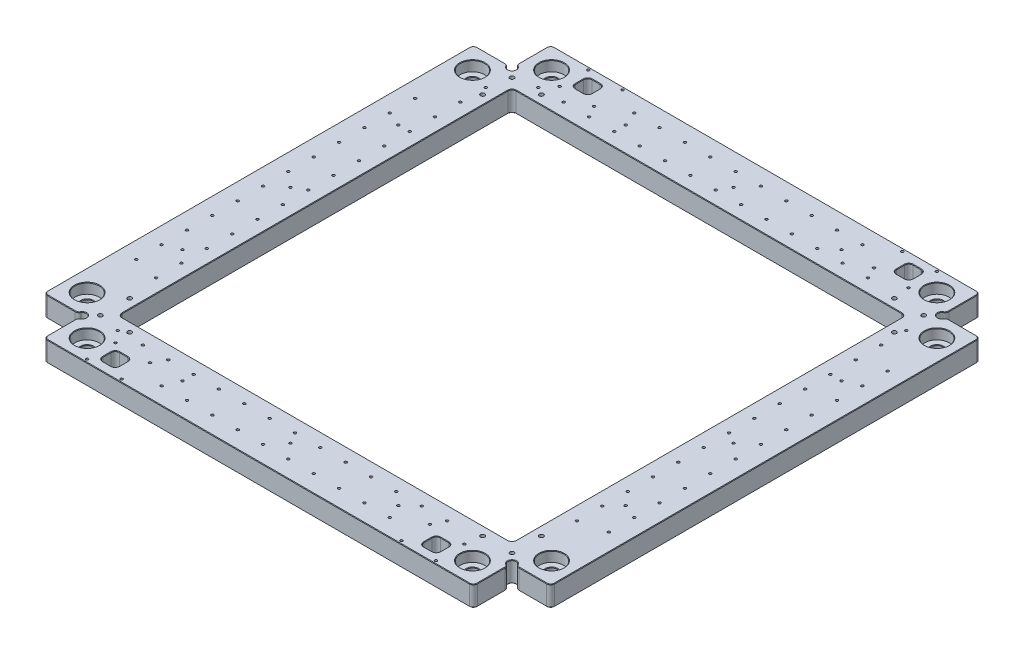
SolidWorks part; units mm, degrees
note: '?' marks a value the reader was unsure of.
material "ASTM A36 Steel"
ref_plane "Front Plane" through (0, 0, 0) normal (0, 0, 1) x (1, 0, 0)
ref_plane "Top Plane" through (0, 0, 0) normal (0, 1, 0) x (1, 0, 0)
ref_plane "Right Plane" through (0, 0, 0) normal (1, 0, 0) x (0, 0, -1)
sketch "Sketch1" plane through (0, 0, 0) normal (0, 1, 0) x (1, 0, 0)
  line L1 (250, -250) -> (-250, -250)
  line L2 (250, -250) -> (250, 250)
  line L3 (250, 250) -> (-250, 250)
  line L4 (-250, -250) -> (-250, 250)
  line L5 (250, -250) -> (-250, 250) construction
  line L6 (250, 250) -> (-250, -250) construction
  point P0 (0, 0)
  dimension "D1" = 500
  dimension "D2" = 500
extrude "Boss-Extrude1" add sketch "Sketch1" along normal blind 20
sketch "Sketch2" plane through (0, 20, 0) normal (0, 1, 0) x (1, 0, 0)
  line L0 (250, 250) -> (-250, 250) construction
  line L10 (-250, 250) -> (-250, -250) construction
  line L15 (-250, 169) -> (-208, 169)
  line L16 (-250, 169) -> (-250, 211)
  line L17 (-174.5, 213.5) -> (-205.5, 213.5)
  line L27 (-250, 211) -> (-208, 211)
  line L33 (-208, 169) -> (-208, 211)
  line L35 (-250, 169) -> (-208, 211) construction
  line L36 (-250, 211) -> (-208, 169) construction
  line L37 (-169, 208) -> (-211, 208)
  line L38 (-169, 208) -> (-169, 250)
  line L39 (-169, 250) -> (-211, 250)
  line L40 (-211, 208) -> (-211, 250)
  line L41 (-169, 208) -> (-211, 250) construction
  line L42 (-169, 250) -> (-211, 208) construction
  line L43 (-208, 206) -> (-213, 211)
  line L44 (-174.5, 213.5) -> (-174.5, 244.5)
  line L45 (-174.5, 244.5) -> (-205.5, 244.5)
  line L46 (-205.5, 213.5) -> (-205.5, 244.5)
  line L47 (-174.5, 213.5) -> (-205.5, 244.5) construction
  line L48 (-174.5, 244.5) -> (-205.5, 213.5) construction
  line L49 (-213.5, 174.5) -> (-244.5, 174.5)
  line L50 (-213.5, 174.5) -> (-213.5, 205.5)
  line L51 (-213.5, 205.5) -> (-244.5, 205.5)
  line L52 (-244.5, 174.5) -> (-244.5, 205.5)
  line L53 (-213.5, 174.5) -> (-244.5, 205.5) construction
  line L54 (-213.5, 205.5) -> (-244.5, 174.5) construction
  line L55 (-206, 208) -> (-211, 213)
  line L56 (-213, 211) -> (-211, 213) construction
  point P1 (-229, 190)
  point P5 (-190, 229)
  point P23 (-229, 190)
  point P27 (-190, 229)
  dimension "D1" = 5
  dimension "D2" = 45
  dimension "D3" = 42
  dimension "D4" = 31
  dimension "D5" = 45
  dimension "D6" = 5
  dimension "D7" = 60
hole_wizard "Bearing Press Fit" positions "Sketch8" profile "Sketch9" hole size "Ø11.8" standard "ANSI Metric" end condition through all
sketch "Sketch8" plane through (0, 20, 0) normal (0, 1, 0) x (1, 0, 0)
  line L1 (-169, 250) -> (-211, 208) construction
  point P8 (-190, 229)
  point P12 (-229, 190)
sketch "Sketch9" plane through (-190, 20, -229) normal (1, 0, 0) x (0, 0, 1)
  line L0 (0, 0) -> (0, 20)
  line L1 (0, 20) -> (5.9, 20)
  line L2 (5.9, 20) -> (5.9, 0)
  line L5 (5.9, 0) -> (0, 0)
  line L11 (0, -6.35) -> (0, 107.95) construction
  dimension "Thru Hole Dia." = 11.8
  dimension "Thru Hole Depth" = 20
ref_axis "Axis1" through (0, 21, 0) along (0, -1, 0)?
pattern_circular "CirPattern1" count 4 over 360 about axis through (0, 0, 0) along (0, 1, 0) of "Bearing Press Fit"
sketch "Sketch5" plane through (0, 20, 0) normal (0, 1, 0) x (1, 0, 0)
  line L1 (194, -194) -> (-194, -194)
  line L2 (194, -194) -> (194, 194)
  line L3 (194, 194) -> (-194, 194)
  line L4 (-194, -194) -> (-194, 194)
  line L5 (194, -194) -> (-194, 194) construction
  line L6 (194, 194) -> (-194, -194) construction
  point P0 (0, 0)
  dimension "D1" = 388
extrude "Cut-Extrude1" cut sketch "Sketch5" against normal up to surface (20 mm away) up to face at (-229, 0, 195.9)
sketch "Sketch10" plane through (0, 0, 0) normal (0, 1, 0) x (1, 0, 0)
  line L5 (194, 194) -> (-194, 194) construction
  line L6 (214, -214) -> (-214, -214)
  line L14 (214, -214) -> (214, 214)
  line L15 (214, 214) -> (-214, 214)
  line L16 (-214, -214) -> (-214, 214)
  line L17 (214, -214) -> (-214, 214) construction
  line L18 (214, 214) -> (-214, -214) construction
  line L19 (201.5, -201.5) -> (-201.5, -201.5)
  line L20 (201.5, -201.5) -> (201.5, 201.5)
  line L21 (201.5, 201.5) -> (-201.5, 201.5)
  line L22 (-201.5, -201.5) -> (-201.5, 201.5)
  line L23 (201.5, -201.5) -> (-201.5, 201.5) construction
  line L24 (201.5, 201.5) -> (-201.5, -201.5) construction
  point P0 (0, 0)
  point P6 (0, 0)
  dimension "D2" = 7.5
  dimension "D1" = 12.5
extrude "Linear Rail Slot" cut sketch "Sketch10" along normal blind 2.5
fillet "Fillet2" radius 4 4 edges at (-194, 10, 194) (194, 10, 194) (194, 10, -194) (-194, 10, -194)
sketch "Sketch11" plane through (0, 2.5, 0) normal (0, -1, 0) x (1, 0, 0)
  line L0 (-204, 207.5) -> (156, 207.5)
  line L1 (-201.5, 201.5) -> (201.5, 201.5) construction
  line L3 (-214, -214) -> (-214, 214) construction
  point P16 (143.5, 207.5)
  point P18 (118.5, 207.5)
  point P19 (93.5, 207.5)
  point P20 (68.5, 207.5)
  point P21 (43.5, 207.5)
  point P22 (18.5, 207.5)
  point P23 (-6.5, 207.5)
  point P24 (-31.5, 207.5)
  point P25 (-56.5, 207.5)
  point P26 (-81.5, 207.5)
  point P28 (-106.5, 207.5)
  point P29 (-131.5, 207.5)
  point P30 (-156.5, 207.5)
  point P31 (-181.5, 207.5)
  dimension "D1" = 360
  dimension "D2" = 6
  dimension "D4" = 14
  dimension "D5" = 25
  dimension "D6" = 10
  dimension "D3" = 12.5
hole_wizard "Tap Drill for M3x0.5 Tap1" positions "Sketch12" profile "Sketch13" hole size "M3x0.5" standard "ANSI Metric" end condition through all
sketch "Sketch12" plane through (0, 2.5, 0) normal (0, -1, 0) x (-1, 0, 0)
  line L0 (204, -207.5) -> (-156, -207.5) construction
  point P28 (-143.5, -207.5)
  point P31 (-118.5, -207.5)
  point P34 (-93.5, -207.5)
  point P37 (-68.5, -207.5)
  point P40 (-43.5, -207.5)
  point P43 (-18.5, -207.5)
  point P46 (6.5, -207.5)
  point P49 (31.5, -207.5)
  point P51 (56.5, -207.5)
  point P54 (81.5, -207.5)
  point P57 (106.5, -207.5)
  point P61 (131.5, -207.5)
  point P64 (156.5, -207.5)
  point P67 (181.5, -207.5)
sketch "Sketch13" plane through (143.5, 2.5, 207.5) normal (1, 0, 0) x (0, 0, -1)
  line L0 (0, 0) -> (0, 17.5)
  line L1 (0, 17.5) -> (1.25, 17.5)
  line L2 (1.25, 17.5) -> (1.25, 0)
  line L5 (1.25, 0) -> (0, 0)
  line L11 (0, -6.35) -> (0, 107.95) construction
  dimension "Thru Hole Dia." = 2.5
  dimension "Thru Hole Depth" = 17.5
sketch "Sketch14" plane through (0, 0, 0) normal (0, -1, 0) x (1, 0, 0)
  line L1 (-156.5, 213.5) -> (-181.5, 213.5)
  line L2 (-152.5, 217.5) -> (-152.5, 219.5)
  line L3 (-156.5, 223.5) -> (-181.5, 223.5)
  line L4 (-185.5, 217.5) -> (-185.5, 219.5)
  line L5 (-152.5, 213.5) -> (-185.5, 223.5) construction
  line L6 (-152.5, 223.5) -> (-185.5, 213.5) construction
  line L7 (-201.5, 201.5) -> (201.5, 201.5) construction
  line L8 (-181.5, 207.5) -> (-156.5, 207.5) construction
  line L19 (-6.5, 213.5) -> (-31.5, 213.5)
  line L25 (-2.5, 217.5) -> (-2.5, 219.5)
  line L26 (-6.5, 223.5) -> (-31.5, 223.5)
  line L31 (-35.5, 217.5) -> (-35.5, 219.5)
  line L32 (-2.5, 213.5) -> (-35.5, 223.5) construction
  line L33 (-2.5, 223.5) -> (-35.5, 213.5) construction
  line L34 (-31.5, 207.5) -> (-6.5, 207.5) construction
  line L35 (143.5, 213.5) -> (118.5, 213.5)
  line L36 (147.5, 217.5) -> (147.5, 219.5)
  line L37 (143.5, 223.5) -> (118.5, 223.5)
  line L38 (114.5, 217.5) -> (114.5, 219.5)
  line L39 (147.5, 213.5) -> (114.5, 223.5) construction
  line L40 (147.5, 223.5) -> (114.5, 213.5) construction
  line L41 (118.5, 207.5) -> (143.5, 207.5) construction
  arc A3 (-152.5, 219.5) -> (-156.5, 223.5) centre (-156.5, 219.5) ccw
  arc A4 (-156.5, 213.5) -> (-152.5, 217.5) centre (-156.5, 217.5) ccw
  arc A5 (-181.5, 213.5) -> (-185.5, 217.5) centre (-181.5, 217.5) cw
  arc A6 (-181.5, 223.5) -> (-185.5, 219.5) centre (-181.5, 219.5) ccw
  arc A7 (-2.5, 219.5) -> (-6.5, 223.5) centre (-6.5, 219.5) ccw
  arc A8 (-6.5, 213.5) -> (-2.5, 217.5) centre (-6.5, 217.5) ccw
  arc A9 (-31.5, 213.5) -> (-35.5, 217.5) centre (-31.5, 217.5) cw
  arc A10 (-31.5, 223.5) -> (-35.5, 219.5) centre (-31.5, 219.5) ccw
  arc A11 (147.5, 219.5) -> (143.5, 223.5) centre (143.5, 219.5) ccw
  arc A12 (143.5, 213.5) -> (147.5, 217.5) centre (143.5, 217.5) ccw
  arc A13 (118.5, 213.5) -> (114.5, 217.5) centre (118.5, 217.5) cw
  arc A14 (118.5, 223.5) -> (114.5, 219.5) centre (118.5, 219.5) ccw
  point P0 (-169, 218.5)
  point P12 (-169, 207.5)
  point P26 (-19, 218.5)
  point P45 (131, 218.5)
  dimension "D5" = 3
  dimension "D4" = 4
  dimension "D1" = 33
  dimension "D2" = 12
  dimension "D3" = 10
  dimension "D7" = 25
  dimension "D6" = 150
mirror "Mirror5" about plane through (0, 0, 0) normal (0, 0, 1) of "Tap Drill for M3x0.5 Tap1"
ref_plane "Plane1" through (0, 0, 0) normal (-0.7071, 0, 0.7071) x (0.7071, 0, 0.7071)
mirror "Mirror6" about plane through (0, 0, 0) normal (-0.7071, 0, 0.7071) of "Mirror5", "Tap Drill for M3x0.5 Tap1"
sketch "Sketch19" plane through (0, 2.5, 0) normal (0, -1, 0) x (1, 0, 0)
  line L0 (-198.5, 201.5) -> (-198.5, 214)
  line L1 (-201.5, 201.5) -> (201.5, 201.5) construction
  line L2 (-214, 214) -> (214, 214) construction
  line L3 (-198.5, 214) -> (-214, 214)
  line L4 (-214, 214) -> (-214, 198.5)
  line L5 (-214, -214) -> (-214, 214) construction
  line L6 (-214, 198.5) -> (-201.5, 198.5)
  line L7 (-201.5, -201.5) -> (-201.5, 201.5) construction
  line L8 (-201.5, 198.5) -> (-201.5, 201.5)
  line L9 (-201.5, 201.5) -> (-198.5, 201.5)
  dimension "D1" = 3
extrude "Boss-Extrude2" add sketch "Sketch19" along normal up to surface (2.5 mm away) up to face at (-229, 0, 195.9)
pattern_circular "CirPattern4" count 4 over 360 about axis through (0, 0, 0) along (0, 1, 0) of "Boss-Extrude2"
sketch "Sketch20" plane through (0, 20, 0) normal (0, 1, 0) x (1, 0, 0)
  line L5 (-250, -250) -> (250, -250) construction
  line L20 (150.3, -225) -> (166.3, -241) construction
  line L23 (166.3, -225) -> (150.3, -241) construction
  line L28 (122, -247) -> (172, -219) construction
  line L29 (172, -247) -> (122, -219) construction
  line L30 (172, -219) -> (122, -219) construction
  line L31 (122, -247) -> (122, -219) construction
  line L32 (172, -247) -> (122, -247) construction
  line L33 (172, -247) -> (172, -219) construction
  line L34 (162.3, -241) -> (154.3, -241)
  line L35 (150.3, -229) -> (150.3, -237)
  line L36 (162.3, -225) -> (154.3, -225)
  line L37 (166.3, -229) -> (166.3, -237)
  arc A12 (154.3, -225) -> (150.3, -229) centre (154.3, -229) ccw
  arc A13 (150.3, -237) -> (154.3, -241) centre (154.3, -237) ccw
  arc A14 (166.3, -237) -> (162.3, -241) centre (162.3, -237) cw
  arc A15 (166.3, -229) -> (162.3, -225) centre (162.3, -229) ccw
  circle A16 centre (190, -229) radius 5.9 construction
  point P65 (158.3, -233)
  point P66 (147, -233)
  point P67 (158.3, -233)
  dimension "D7" = 31.7
  dimension "D8" = 11.3
  dimension "D6" = 4
  dimension "D1" = 28
  dimension "D2" = 50
  dimension "D3" = 17
  dimension "D4" = 16
  dimension "D5" = 16
extrude "Cut-Extrude3" cut sketch "Sketch20" against normal through all
hole_wizard "Tap Drill for M3x0.5 Tap6" positions "Sketch39" profile "Sketch40" hole size "M3x0.5" standard "ANSI Metric" end condition through all
sketch "Sketch39" plane through (0, 20, 0) normal (0, 1, 0) x (1, 0, 0)
  line L1 (172, -247) -> (138, -247)
  line L2 (172, -247) -> (172, -219)
  line L3 (172, -219) -> (138, -219)
  line L4 (138, -247) -> (138, -219)
  line L5 (-250, -250) -> (250, -250) construction
  circle A0 centre (190, -229) radius 5.9 construction
  point P1 (172, -247)
  point P2 (138, -219)
  point P99 (172, -219)
  point P100 (138, -247)
  dimension "D1" = 34
  dimension "D2" = 28
  dimension "D3" = 3
  dimension "D4" = 18
sketch "Sketch40" plane through (172, 20, 247) normal (1, 0, 0) x (0, 0, 1)
  line L0 (0, 0) -> (0, 20)
  line L1 (0, 20) -> (1.25, 20)
  line L2 (1.25, 20) -> (1.25, 0)
  line L5 (1.25, 0) -> (0, 0)
  line L11 (0, -6.35) -> (0, 107.95) construction
  dimension "Thru Hole Dia." = 2.5
  dimension "Thru Hole Depth" = 20
mirror "Mirror8" about plane through (0, 0, 0) normal (1, 0, 0) of "Tap Drill for M3x0.5 Tap6", "Cut-Extrude3"
mirror "Mirror9" about plane through (0, 0, 0) normal (0, 0, 1) of "Mirror8", "Cut-Extrude3", "Tap Drill for M3x0.5 Tap6"
sketch "Sketch27" plane through (0, 20, 0) normal (0, 1, 0) x (1, 0, 0)
  line L1 (250, -250) -> (211.9, -250)
  line L2 (250, -250) -> (250, -211.9)
  line L3 (250, -211.9) -> (211.9, -211.9)
  line L4 (211.9, -250) -> (211.9, -211.9)
  dimension "D1" = 38.1
extrude "Cut-Extrude4" cut sketch "Sketch27" against normal up to surface (20 mm away) up to face at (172, 0, -245.75)
sketch "Sketch47" plane through (0, 0, 0) normal (0, -1, 0) x (1, 0, 0)
  circle A0 centre (211.9, 211.9) radius 4
  dimension "D1" = 8
extrude "Cut-Extrude5" cut sketch "Sketch47" against normal up to surface (20 mm away) up to face at (70.6333, 20, 70.6333)
hole_wizard "Tap Drill for M5x0.8 Tap1" positions "Sketch50" profile "Sketch49" hole size "M5x0.8" standard "ANSI Metric"
sketch "Sketch50" plane through (0, 20, 0) normal (0, 1, 0) x (1, 0, 0)
  line L0 (250, -211.9) -> (250, 250) construction
  line L1 (-250, -250) -> (211.9, -250) construction
  line L2 (174, -203) -> (203, -203) construction
  line L3 (203, -203) -> (203, -174) construction
  point P0 (174, -203)
  point P2 (203, -203)
  point P4 (203, -174)
  dimension "D1" = 47
  dimension "D2" = 29
  dimension "D3" = 47
sketch "Sketch49" plane through (174, 20, 203) normal (1, 0, 0) x (0, 0, 1)
  line L0 (0, 0) -> (0, 11.2618)
  line L1 (0, 11.2618) -> (2.1, 10)
  line L2 (2.1, 10) -> (2.1, 0)
  line L5 (2.1, 0) -> (0, 0)
  line L10 (0, 11.2618) -> (-2.1, 10) construction
  line L11 (0, -6.35) -> (0, 107.95) construction
  dimension "Hole Dia." = 4.2
  dimension "Hole Depth" = 10
  dimension "Drill Angle" = 118
sketch "Sketch53" plane through (0, 0, 0) normal (0, -1, 0) x (1, 0, 0)
  line L0 (-150.3, 233) -> (150.3, 233) construction
  line L1 (-150.3, 229) -> (-150.3, 237) construction
  line L2 (150.3, 229) -> (150.3, 237) construction
  line L3 (-112.5, 233) -> (-166.3, 233) construction
  line L4 (-166.3, 237) -> (-166.3, 229) construction
  line L5 (112.5, 233) -> (166.3, 233) construction
  line L6 (166.3, 237) -> (166.3, 229) construction
  point P6 (-112.5, 233)
  point P7 (-87.5, 233)
  point P9 (-62.5, 233)
  point P10 (-37.5, 233)
  point P11 (-12.5, 233)
  point P12 (12.5, 233)
  point P13 (37.5, 233)
  point P14 (62.5, 233)
  point P15 (87.5, 233)
  point P16 (112.5, 233)
  point P26 (137.5, 233)
  dimension "D3" = 25
  dimension "D2" = 11
hole_wizard "Tap Drill for M3x0.5 Tap7" positions "Sketch54" profile "Sketch56" hole size "M3x0.5" standard "ANSI Metric" end condition through all
sketch "Sketch54" plane through (0, 0, 0) normal (0, -1, 0) x (-1, 0, 0)
  point P0 (-112.5, -233)
  point P3 (-87.5, -233)
  point P6 (-62.5, -233)
  point P9 (-37.5, -233)
  point P12 (-12.5, -233)
  point P15 (12.5, -233)
  point P18 (37.5, -233)
  point P21 (62.5, -233)
  point P24 (87.5, -233)
  point P27 (112.5, -233)
sketch "Sketch56" plane through (112.5, 0, 233) normal (1, 0, 0) x (0, 0, -1)
  line L0 (0, 0) -> (0, 20)
  line L1 (0, 20) -> (1.25, 20)
  line L2 (1.25, 20) -> (1.25, 0)
  line L5 (1.25, 0) -> (0, 0)
  line L11 (0, -6.35) -> (0, 107.95) construction
  dimension "Thru Hole Dia." = 2.5
  dimension "Thru Hole Depth" = 20
sketch "Sketch59" plane through (0, 0, 0) normal (0, -1, 0) x (1, 0, 0)
  line L0 (-198.5, 201.5) -> (198.5, 201.5) construction
  line L4 (-94, 213.5) -> (-119, 213.5)
  line L5 (-90, 217.5) -> (-90, 219.5)
  line L6 (-94, 223.5) -> (-119, 223.5)
  line L7 (-123, 217.5) -> (-123, 219.5)
  line L8 (-90, 213.5) -> (-123, 223.5) construction
  line L9 (-90, 223.5) -> (-123, 213.5) construction
  line L10 (-106.5, 207.5) -> (-106.5, 218.5) construction
  line L11 (-12.5, 233) -> (12.5, 233) construction
  arc A2 (-90, 219.5) -> (-94, 223.5) centre (-94, 219.5) ccw
  arc A3 (-94, 213.5) -> (-90, 217.5) centre (-94, 217.5) ccw
  arc A4 (-119, 213.5) -> (-123, 217.5) centre (-119, 217.5) cw
  arc A5 (-119, 223.5) -> (-123, 219.5) centre (-119, 219.5) ccw
  point P0 (-106.5, 218.5)
  dimension "D1" = 10
  dimension "D4" = 4
  dimension "D2" = 33
  dimension "D3" = 12
extrude "Cut-Extrude6" cut sketch "Sketch59" against normal blind 3.5
hole_wizard "Tap Drill for M3x0.5 Tap9" positions "Sketch62" profile "Sketch63" hole size "M3x0.5" standard "ANSI Metric" end condition through all
sketch "Sketch62" plane through (0, 3.5, 0) normal (0, -1, 0) x (-1, 0, 0)
  line L0 (90, -218.5) -> (123, -218.5) construction
  line L1 (90, -217.5) -> (90, -219.5) construction
  line L2 (123, -219.5) -> (123, -217.5) construction
  point P9 (106.5, -218.5)
sketch "Sketch63" plane through (-106.5, 3.5, 218.5) normal (1, 0, 0) x (0, 0, -1)
  line L0 (0, 0) -> (0, 16.5)
  line L1 (0, 16.5) -> (1.25, 16.5)
  line L2 (1.25, 16.5) -> (1.25, 0)
  line L5 (1.25, 0) -> (0, 0)
  line L11 (0, -6.35) -> (0, 107.95) construction
  dimension "Thru Hole Dia." = 2.5
  dimension "Thru Hole Depth" = 16.5
pattern_linear "LPattern1" count 3 spacing 106.5 along (1, 0, 0) of "Cut-Extrude6", "Tap Drill for M3x0.5 Tap9"
pattern_circular "CirPattern3" count 4 over 360 about axis through (0, 0, 0) along (0, 1, 0) of "Cut-Extrude4", "Cut-Extrude5", "Tap Drill for M5x0.8 Tap1", "Tap Drill for M3x0.5 Tap7", "LPattern1", "Cut-Extrude6", "Tap Drill for M3x0.5 Tap9"
fillet "Fillet8" radius 4 40 edges at (92.0635, 1.25, 214) (198.5, 1.25, 214) (198.5, 1.25, 201.5) (-198.5, 1.25, 201.5) (-198.5, 1.25, 214) (-120.9365, 1.25, 214) (-92.0635, 1.25, 214) (-14.4365, 1.25, 214) (14.4365, 1.25, 214) (120.9365, 1.25, 214) (-214, 1.25, -198.5) (-201.5, 1.25, -198.5) (-201.5, 1.25, 198.5) (-214, 1.25, 198.5) (-214, 1.25, 120.9365) (-214, 1.25, 14.4365) (-214, 1.25, 92.0635) (-214, 1.25, -92.0635) (-214, 1.25, -14.4365) (-214, 1.25, -120.9365) (198.5, 1.25, -214) (198.5, 1.25, -201.5) (-198.5, 1.25, -201.5) (-198.5, 1.25, -214) (-120.9365, 1.25, -214) (-14.4365, 1.25, -214) (-92.0635, 1.25, -214) (92.0635, 1.25, -214) (14.4365, 1.25, -214) (120.9365, 1.25, -214) (214, 1.25, -120.9365) (214, 1.25, -198.5) (214, 1.25, -14.4365) (214, 1.25, -92.0635) (214, 1.25, 92.0635) (214, 1.25, 14.4365) (214, 1.25, 120.9365) (214, 1.25, 198.5) (201.5, 1.25, -198.5) (201.5, 1.25, 198.5)
hole_wizard "Ø24.0 (24) Diameter Hole1" positions "Sketch41" profile "Sketch42" hole size "Ø24.0" standard "ANSI Metric"
sketch "Sketch41" plane through (0, 20, 0) normal (0, 1, 0) x (1, 0, 0)
  point P0 (-229, -190)
  point P3 (-190, -229)
  point P6 (190, -229)
  point P9 (229, -190)
  point P12 (229, 190)
  point P15 (190, 229)
  point P18 (-190, 229)
  point P21 (-229, 190)
sketch "Sketch42" plane through (-229, 20, 190) normal (1, 0, 0) x (0, 0, 1)
  line L0 (0, 0) -> (0, 10)
  line L1 (0, 10) -> (12, 10)
  line L2 (12, 10) -> (12, 0)
  line L5 (12, 0) -> (0, 0)
  line L10 (0, 10) -> (-12, 10) construction
  line L11 (0, -6.35) -> (0, 107.95) construction
  dimension "Hole Dia." = 24
  dimension "Hole Depth" = 10
  dimension "Drill Angle" = 180
fillet "Fillet6" radius 4 16 edges at (250, 10, -211.9) (211.9, 10, -250) (-211.9, 10, -250) (-250, 10, -211.9) (211.9, 10, 250) (250, 10, 211.9) (-211.9, 10, 250) (-250, 10, 211.9) (-215.9, 10, 211.9) (-215.9, 10, -211.9) (-211.9, 10, -215.9) (211.9, 10, -215.9) (215.9, 10, -211.9) (211.9, 10, 215.9) (-211.9, 10, 215.9) (215.9, 10, 211.9)
hole_wizard "Tap Drill for M3x0.5 Tap8" positions "Sketch57" profile "Sketch58" hole size "M3x0.5" standard "ANSI Metric" end condition through all
sketch "Sketch57" plane through (0, 0, 0) normal (0, -1, 0) x (-1, 0, 0)
  line L1 (-233, -137.5) -> (233, -137.5)
  line L2 (-233, -137.5) -> (-233, 137.5)
  line L3 (-233, 137.5) -> (233, 137.5)
  line L4 (233, -137.5) -> (233, 137.5)
  line L5 (-233, -137.5) -> (233, 137.5) construction
  circle A1 centre (233, 112.5) radius 1.25 construction
  point P0 (-233, 137.5)
  point P2 (233, 137.5)
  point P4 (233, -137.5)
  point P6 (-233, -137.5)
  point P111 (0, 0)
  point P117 (-233, 62.5)
  dimension "D1" = 25
sketch "Sketch58" plane through (233, 0, -137.5) normal (1, 0, 0) x (0, 0, -1)
  line L0 (0, 0) -> (0, 20)
  line L1 (0, 20) -> (1.25, 20)
  line L2 (1.25, 20) -> (1.25, 0)
  line L5 (1.25, 0) -> (0, 0)
  line L11 (0, -6.35) -> (0, 107.95) construction
  dimension "Thru Hole Dia." = 2.5
  dimension "Thru Hole Depth" = 20
chamfer "Chamfer1" distance 0.5 angle 45 168 edges at (-150.3, 20, 233) (-150.3, 0, 233) (-151.4716, 20, 239.8284) (-151.4716, 0, 239.8284) (-151.4716, 20, 226.1716) (-151.4716, 0, 226.1716) (-158.3, 20, 241) (-158.3, 0, 241) (-158.3, 20, 225) (-158.3, 0, 225) (-165.1284, 20, 239.8284) (-165.1284, 0, 239.8284) (-165.1284, 20, 226.1716) (-165.1284, 0, 226.1716) (-166.3, 20, 233) (-166.3, 0, 233) (-150.3, 20, -233) (-150.3, 0, -233) (-151.4716, 20, -239.8284) (-151.4716, 0, -239.8284) (-151.4716, 20, -226.1716) (-151.4716, 0, -226.1716) (-158.3, 20, -241) (-158.3, 0, -241) (-158.3, 20, -225) (-158.3, 0, -225) (-165.1284, 20, -239.8284) (-165.1284, 0, -239.8284) (-165.1284, 20, -226.1716) (-165.1284, 0, -226.1716) (-166.3, 20, -233) (-166.3, 0, -233) (166.3, 20, -233) (166.3, 0, -233) (165.1284, 20, -226.1716) (165.1284, 0, -226.1716) (165.1284, 20, -239.8284) (165.1284, 0, -239.8284) (158.3, 20, -225) (158.3, 0, -225) (158.3, 20, -241) (158.3, 0, -241) (151.4716, 20, -226.1716) (151.4716, 0, -226.1716) (151.4716, 20, -239.8284) (151.4716, 0, -239.8284) (150.3, 20, -233) (150.3, 0, -233) (166.3, 20, 233) (166.3, 0, 233) (165.1284, 20, 226.1716) (165.1284, 0, 226.1716) (165.1284, 20, 239.8284) (165.1284, 0, 239.8284) (158.3, 20, 225) (158.3, 0, 225) (158.3, 20, 241) (158.3, 0, 241) (151.4716, 20, 226.1716) (151.4716, 0, 226.1716) (151.4716, 20, 239.8284) (151.4716, 0, 239.8284) (150.3, 20, 233) (150.3, 0, 233) (0, 20, -194) (-192.8284, 20, -192.8284) (192.8284, 20, -192.8284) (-194, 20, 0) (194, 20, 0) (-192.8284, 20, 192.8284) (192.8284, 20, 192.8284) (0, 20, 194) (0, 0, -194) (192.8284, 0, -192.8284) (-192.8284, 0, -192.8284) (194, 0, 0) (-194, 0, 0) (192.8284, 0, 192.8284) (-192.8284, 0, 192.8284) (0, 0, 194) (0, 20, -250) (-210.7284, 20, -248.8284) (210.7284, 20, -248.8284) (-211.9, 20, -232.4141) (211.9, 20, -232.4141) (-211.3641, 20, -216.8282) (211.3641, 20, -216.8282) (-209.0716, 20, -209.0716) (209.0716, 20, -209.0716) (-216.8282, 20, -211.3641) (216.8282, 20, -211.3641) (-232.4141, 20, -211.9) (232.4141, 20, -211.9) (-248.8284, 20, -210.7284) (248.8284, 20, -210.7284) (-250, 20, 0) (250, 20, 0) (-248.8284, 20, 210.7284) (248.8284, 20, 210.7284) (-232.4141, 20, 211.9) (232.4141, 20, 211.9) (-216.8282, 20, 211.3641) (216.8282, 20, 211.3641) (-209.0716, 20, 209.0716) (209.0716, 20, 209.0716) (-211.3641, 20, 216.8282) (211.3641, 20, 216.8282) (-211.9, 20, 232.4141) (211.9, 20, 232.4141) (-210.7284, 20, 248.8284) (210.7284, 20, 248.8284) (0, 20, 250) (0, 0, -250) (-210.7284, 0, -248.8284) (210.7284, 0, -248.8284) (-211.9, 0, -232.4141) (211.9, 0, -232.4141) (-211.3641, 0, -216.8282) (211.3641, 0, -216.8282) (-209.0716, 0, -209.0716) (209.0716, 0, -209.0716) (-216.8282, 0, -211.3641) (216.8282, 0, -211.3641) (-232.4141, 0, -211.9) (232.4141, 0, -211.9) (-248.8284, 0, -210.7284) (248.8284, 0, -210.7284) (-250, 0, 0) (250, 0, 0) (-248.8284, 0, 210.7284) (248.8284, 0, 210.7284) (-232.4141, 0, 211.9) (232.4141, 0, 211.9) (-216.8282, 0, 211.3641) (216.8282, 0, 211.3641) (-209.0716, 0, 209.0716) (209.0716, 0, 209.0716) (-211.3641, 0, 216.8282) (211.3641, 0, 216.8282) (-211.9, 0, 232.4141) (211.9, 0, 232.4141) (-210.7284, 0, 248.8284) (210.7284, 0, 248.8284) (0, 0, 250) (-229, 10, 184.1) (-229, 0, 195.9) (-190, 10, 223.1) (-190, 0, 234.9) (229, 10, 184.1) (229, 0, 195.9) (190, 10, 223.1) (190, 0, 234.9) (229, 10, -195.9) (229, 0, -184.1) (190, 10, -234.9) (190, 0, -223.1) (-229, 10, -195.9) (-229, 0, -184.1) (-190, 10, -234.9) (-190, 0, -223.1) (-229, 20, 202) (-190, 20, 241) (229, 20, 202) (190, 20, 241) (229, 20, -178) (190, 20, -217) (-229, 20, -178) (-190, 20, -217)
